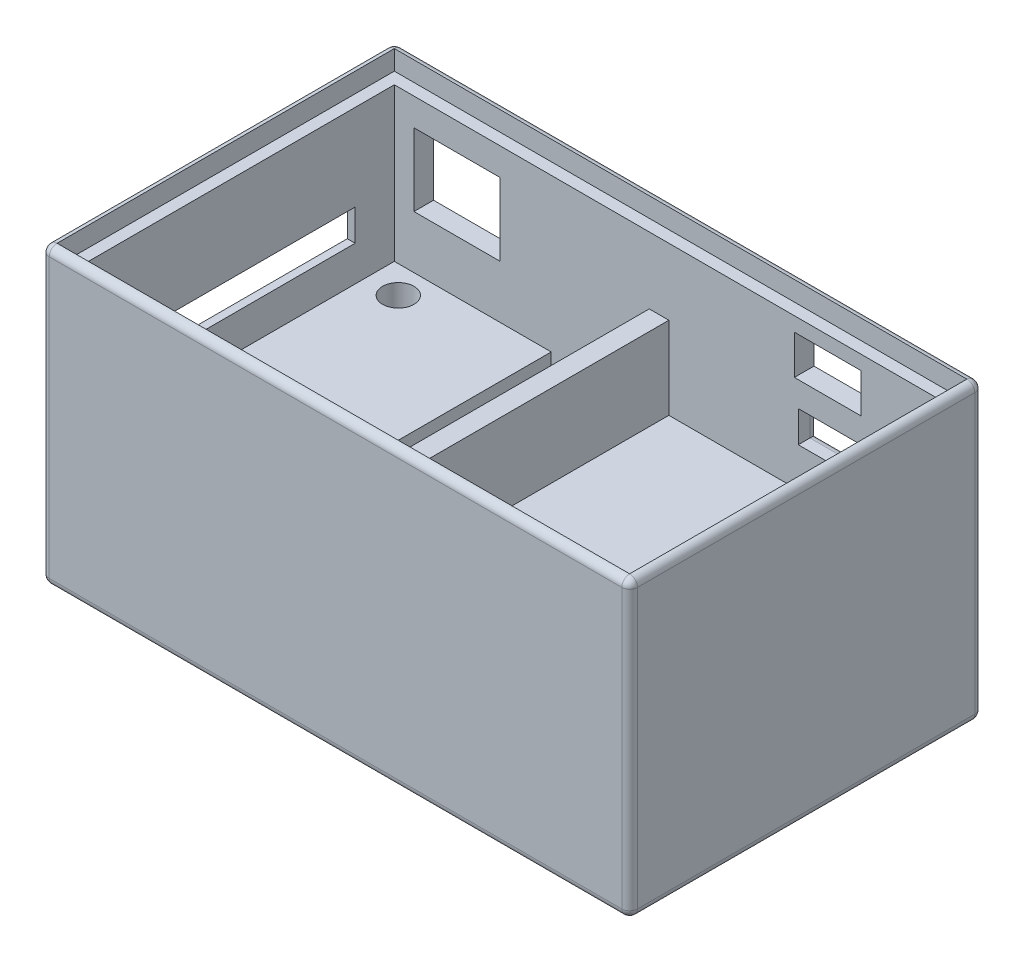
SolidWorks part; units mm, degrees
ref_plane "前视基准面" through (0, 0, 0) normal (0, 0, 1) x (1, 0, 0)
ref_plane "上视基准面" through (0, 0, 0) normal (0, 1, 0) x (1, 0, 0)
ref_plane "右视基准面" through (0, 0, 0) normal (1, 0, 0) x (0, 0, -1)
sketch "草图2" plane through (0, 0, 0) normal (0, 1, 0) x (1, 0, 0)
  line L1 (0, 0) -> (150, 0)
  line L2 (0, 0) -> (0, 90)
  line L3 (0, 90) -> (150, 90)
  line L4 (150, 0) -> (150, 90)
  dimension "D1" = 90
  dimension "D2" = 150
extrude "凸台-拉伸1" add sketch "草图2" along normal blind 75
sketch "草图3" plane through (0, 75, 0) normal (0, 1, 0) x (1, 0, 0)
  line L0 (150, 0) -> (150, 90) construction
  line L1 (5, 85) -> (145, 85)
  line L2 (5, 85) -> (5, 5)
  line L3 (5, 5) -> (145, 5)
  line L4 (145, 85) -> (145, 5)
  line L9 (150, 90) -> (0, 90) construction
  dimension "D1" = 5
  dimension "D2" = 5
  dimension "D3" = 5
  dimension "D4" = 5
extrude "切除-拉伸2" cut sketch "草图3" against normal blind 72
sketch "草图6" plane through (0, 3, 0) normal (0, 1, 0) x (1, 0, 0)
  line L0 (145, 85) -> (5, 85) construction
  line L1 (70, 85) -> (75, 85)
  line L2 (70, 85) -> (70, 5)
  line L3 (70, 5) -> (75, 5)
  line L4 (75, 85) -> (75, 5)
  line L5 (5, 5) -> (145, 5) construction
  line L6 (145, 5) -> (145, 85) construction
  dimension "D1" = 70
  dimension "D2" = 5
extrude "凸台-拉伸2" add sketch "草图6" along normal blind 50
sketch "草图8" plane through (0, 0, -85) normal (0, 0, 1) x (1, 0, 0)
  line L0 (75, 53) -> (75, 3) construction
  line L1 (75, 32) -> (145, 32)
  line L2 (75, 32) -> (75, 29)
  line L3 (75, 29) -> (145, 29)
  line L4 (145, 32) -> (145, 29)
  line L5 (145, 3) -> (75, 3) construction
  line L6 (145, 3) -> (145, 75) construction
  dimension "D1" = 26
  dimension "D2" = 3
  dimension "D3" = 0
extrude "凸台-拉伸3" add sketch "草图8" along normal up to next
sketch "草图9" plane through (70, 0, 0) normal (-1, 0, 0) x (0, 0, 1)
  line L6 (-85, 3) -> (-5, 3) construction
  line L7 (-77, 13) -> (-57, 13)
  line L8 (-77, 13) -> (-77, 3)
  line L9 (-77, 3) -> (-57, 3)
  line L10 (-57, 13) -> (-57, 3)
  line L11 (-85, 53) -> (-85, 3) construction
  dimension "D1" = 20
  dimension "D2" = 10
  dimension "D3" = 8
extrude "切除-拉伸3" cut sketch "草图9" against normal up to next
sketch "草图10" plane through (0, 0, -85) normal (0, 0, 1) x (1, 0, 0)
  line L1 (75, 29) -> (145, 29)
  line L2 (75, 29) -> (75, 3)
  line L3 (75, 3) -> (145, 3)
  line L4 (145, 29) -> (145, 3)
extrude "切除-拉伸4" cut sketch "草图10" against normal up to next
sketch "草图11" plane through (0, 0, -90) normal (0, 0, -1) x (-1, 0, 0)
  line L0 (-145, 29) -> (-145, 3) construction
  line L1 (-147.5, 31.5) -> (-72.5, 31.5)
  line L2 (-147.5, 31.5) -> (-147.5, 1.5)
  line L3 (-147.5, 1.5) -> (-72.5, 1.5)
  line L4 (-72.5, 31.5) -> (-72.5, 1.5)
  line L5 (-75, 29) -> (-145, 29) construction
  line L6 (-75, 3) -> (-145, 3) construction
  line L7 (-75, 29) -> (-75, 3) construction
  dimension "D1" = 2.5
  dimension "D2" = 2.5
  dimension "D3" = 1.5
  dimension "D4" = 2.5
extrude "切除-拉伸5" cut sketch "草图11" against normal blind 5
sketch "草图12" plane through (0, 0, -85) normal (0, 0, 1) x (1, 0, 0)
  line L0 (145, 32) -> (145, 75) construction
  line L1 (108, 50) -> (123, 50)
  line L2 (108, 50) -> (108, 42)
  line L3 (108, 42) -> (123, 42)
  line L4 (123, 50) -> (123, 42)
  line L6 (145, 32) -> (75, 32) construction
  dimension "D1" = 15
  dimension "D2" = 8
  dimension "D3" = 22
  dimension "D4" = 10
extrude "切除-拉伸6" cut sketch "草图12" against normal blind 5
fillet "圆角1" radius 2 20 edges at (75, 75, 0) (150, 37.5, 0) (75, 0, 0) (0, 37.5, -90) (0, 75, -45) (0, 37.5, 0) (0, 0, -45) (75, 75, -90) (75, 0, -90) (72.5, 16.5, -90) (110, 31.5, -90) (147.5, 16.5, -90) (110, 1.5, -90) (123, 46, -90) (115.5, 42, -90) (108, 46, -90) (115.5, 50, -90) (150, 75, -45) (150, 37.5, -90) (150, 0, -45)
sketch "草图13" plane through (0, 0, -85) normal (0, 0, 1) x (1, 0, 0)
  line L0 (5, 3) -> (5, 75) construction
  line L1 (5, 31) -> (45, 31)
  line L2 (5, 31) -> (5, 25)
  line L3 (5, 25) -> (45, 25)
  line L4 (45, 31) -> (45, 25)
  line L5 (70, 3) -> (5, 3) construction
  dimension "D1" = 40
  dimension "D2" = 22
  dimension "D3" = 6
extrude "凸台-拉伸4" add sketch "草图13" along normal up to next
sketch "草图14" plane through (0, 31, 0) normal (0, 1, 0) x (1, 0, 0)
  line L0 (5, 5) -> (5, 85) construction
  line L1 (45, 85) -> (5, 85) construction
  circle A0 centre (13, 78) radius 4
  circle A1 centre (13, 18) radius 4
  dimension "D2" = 8
  dimension "D5" = 8
  dimension "D1" = 8
  dimension "D3" = 7
  dimension "D4" = 60
extrude "切除-拉伸7" cut sketch "草图14" against normal up to next
sketch "草图15" plane through (5, 0, 0) normal (1, 0, 0) x (0, 0, -1)
  line L0 (85, 3) -> (5, 3) construction
  line L1 (18, 12) -> (81, 12)
  line L2 (18, 12) -> (18, 4)
  line L3 (18, 4) -> (81, 4)
  line L4 (81, 12) -> (81, 4)
  line L5 (85, 3) -> (85, 25) construction
  dimension "D1" = 8
  dimension "D2" = 1
  dimension "D3" = 63
  dimension "D4" = 4
extrude "切除-拉伸8" cut sketch "草图15" against normal up to next
sketch "草图16" plane through (5, 0, 0) normal (1, 0, 0) x (0, 0, -1)
  line L0 (5, 31) -> (85, 31) construction
  line L1 (15.5, 48) -> (75, 48)
  line L2 (15.5, 48) -> (15.5, 40)
  line L3 (15.5, 40) -> (75, 40)
  line L4 (75, 48) -> (75, 40)
  line L5 (85, 31) -> (85, 75) construction
  dimension "D1" = 59.5
  dimension "D2" = 8
  dimension "D3" = 9
  dimension "D4" = 10
extrude "切除-拉伸9" cut sketch "草图16" against normal up to next
sketch "草图17" plane through (0, 0, 0) normal (-1, 0, 0) x (0, 0, 1)
  line L0 (-88, 2) -> (-2, 2) construction
  line L1 (-85.4, 56) -> (-15.4, 56)
  line L2 (-85.4, 56) -> (-85.4, 4)
  line L3 (-85.4, 4) -> (-15.4, 4)
  line L4 (-15.4, 56) -> (-15.4, 4)
  line L5 (-88, 73) -> (-88, 2) construction
  dimension "D1" = 70
  dimension "D2" = 52
  dimension "D3" = 2
  dimension "D4" = 2.6
extrude "切除-拉伸10" cut sketch "草图17" against normal blind 3
sketch "草图18" plane through (0, 0, -85) normal (0, 0, 1) x (1, 0, 0)
  line L0 (145, 75) -> (5, 75) construction
  line L1 (10, 63) -> (32, 63)
  line L2 (10, 63) -> (10, 44.5)
  line L3 (10, 44.5) -> (32, 44.5)
  line L4 (32, 63) -> (32, 44.5)
  line L5 (5, 31) -> (5, 75) construction
  dimension "D1" = 22
  dimension "D2" = 18.5
  dimension "D3" = 12
  dimension "D4" = 5
extrude "切除-拉伸11" cut sketch "草图18" against normal up to next
sketch "草图19" plane through (0, 75, 0) normal (0, 1, 0) x (1, 0, 0)
  line L0 (148, 88) -> (2, 88) construction
  line L1 (2, 88) -> (148, 88)
  line L2 (2, 88) -> (2, 2)
  line L3 (2, 2) -> (148, 2)
  line L4 (148, 88) -> (148, 2)
  line L5 (2, 88) -> (2, 2) construction
extrude "切除-拉伸12" cut sketch "草图19" against normal blind 5
sketch "草图20" plane through (0, 0, -90) normal (0, 0, -1) x (-1, 0, 0)
  line L0 (-148, 73) -> (-148, 33.5) construction
  line L1 (-124, 66.3711) -> (-107, 66.3711)
  line L2 (-124, 66.3711) -> (-124, 56.3711)
  line L3 (-124, 56.3711) -> (-107, 56.3711)
  line L4 (-107, 66.3711) -> (-107, 56.3711)
  dimension "D1" = 17
  dimension "D2" = 10
  dimension "D3" = 24
extrude "切除-拉伸13" cut sketch "草图20" against normal up to next
